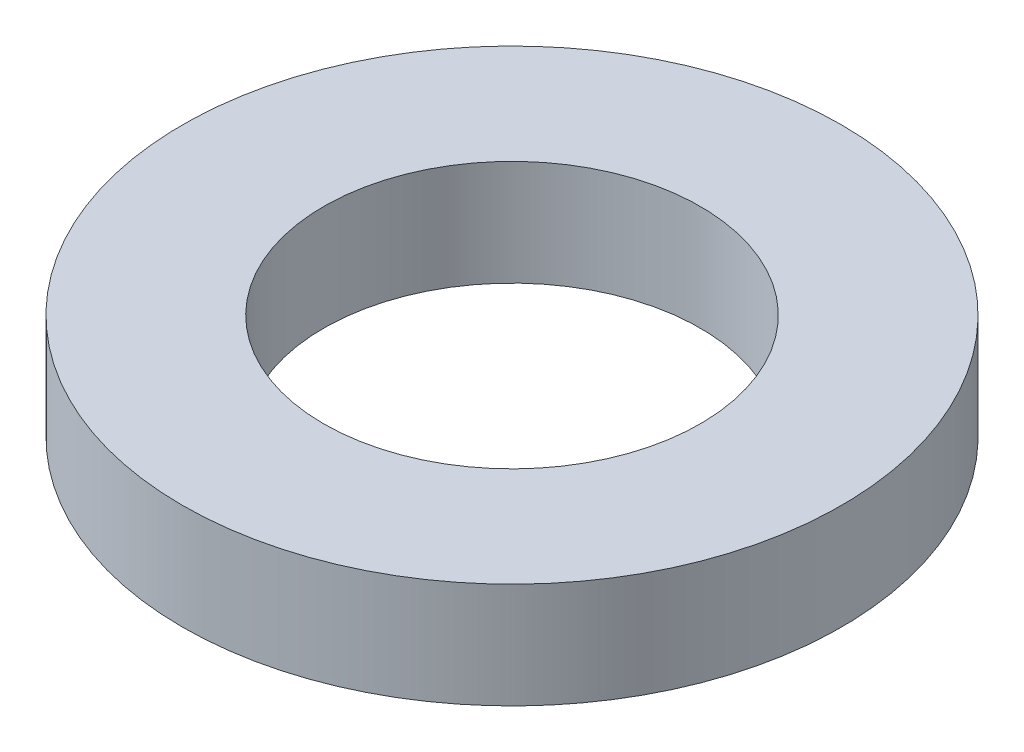
SolidWorks part; units mm, degrees
ref_plane "Front Plane" through (0, 0, 0) normal (0, 0, 1) x (1, 0, 0)
ref_plane "Top Plane" through (0, 0, 0) normal (0, 1, 0) x (1, 0, 0)
ref_plane "Right Plane" through (0, 0, 0) normal (1, 0, 0) x (0, 0, -1)
sketch "Sketch1" plane through (0, 0, 0) normal (0, 1, 0) x (1, 0, 0)
  circle A0 centre (0, 0) radius 87.5
  dimension "FLANGE_OD" = 175
extrude "Boss-Extrude1" add sketch "Sketch1" along normal blind 28
sketch "Sketch2" plane through (0, 0, 0) normal (0, 1, 0) x (1, 0, 0)
  circle A0 centre (0, 0) radius 50
  dimension "BORE_D" = 100
extrude "Cut-Extrude1" cut sketch "Sketch2" along normal through all
sketch "Sketch3" plane through (0, 28, 0) normal (0, 1, 0) x (1, 0, 0)
  circle A0 centre (0, 0) radius 32.6651 construction
  circle A1 centre (-32.6651, 0) radius 1.8172
  dimension "BOLT_D" = 3.6345
  dimension "BOLT_PCD" = 65.3301
extrude "Cut-Extrude2" cut sketch "Sketch3" against normal blind 21.9706 rebuild error yes
pattern_circular "CirPattern1" count 4 over 360 rebuild error yes
